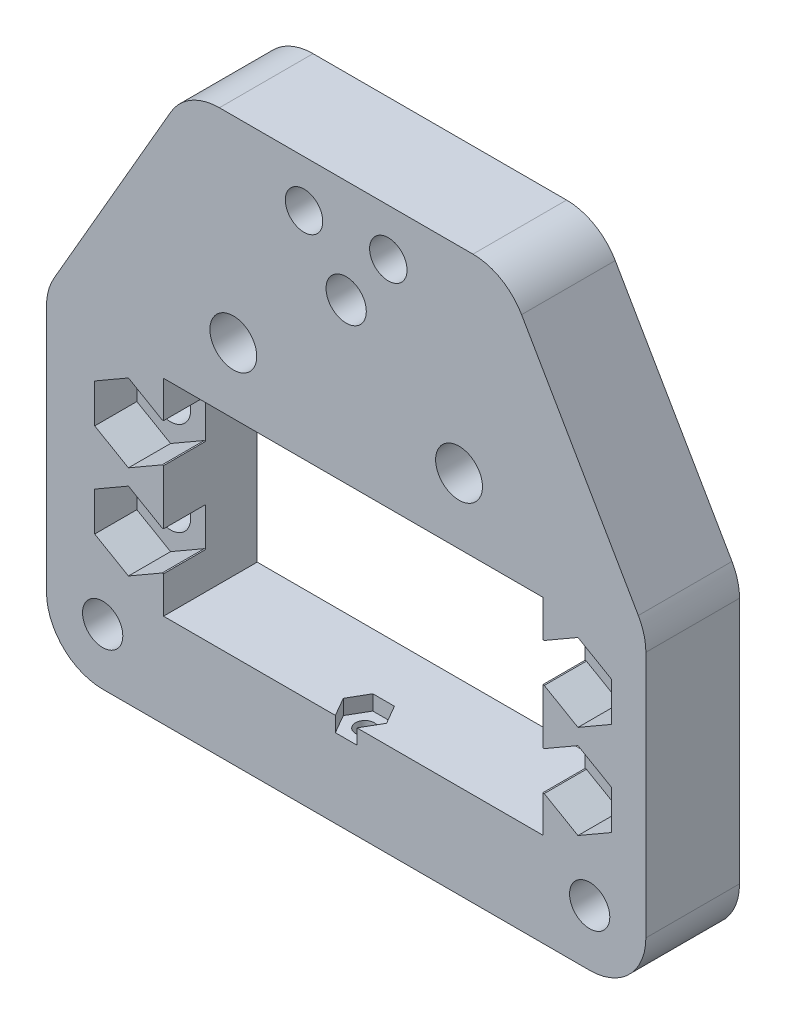
SolidWorks part; units mm, degrees
material "ABS"
ref_plane "Спереди" through (0, 0, 0) normal (0, 0, 1) x (1, 0, 0)
ref_plane "Сверху" through (0, 0, 0) normal (0, 1, 0) x (1, 0, 0)
ref_plane "Справа" through (0, 0, 0) normal (1, 0, 0) x (0, 0, -1)
sketch "Эскиз1" plane through (0, 0, 0) normal (0, 0, 1) x (1, 0, 0)
  line L0 (0, 0) -> (64, 0)
  line L1 (64, 0) -> (64, 34.0192)
  line L2 (64, 34.0192) -> (49, 60)
  line L3 (49, 60) -> (15, 60)
  line L4 (15, 60) -> (0, 34.02)
  line L5 (0, 34.02) -> (0, 0)
  dimension "D1" = 64
  dimension "D2" = 60
  dimension "D3" = 34
  dimension "D4" = 30
  dimension "D5" = 120
  dimension "D6" = 34.02
extrude "Бобышка-Вытянуть1" add sketch "Эскиз1" along normal blind 10 contours L0 L1 L2 L3 L4 L5
fillet "Скругление1" radius 6 6 edges at (49, 60, 5) (15, 60, 5) (0, 34.02, 5) (0, 0, 5) (64, 34.0192, 5) (64, 0, 5)
sketch "Эскиз2" plane through (0, 0, 10) normal (0, 0, 1) x (1, 0, 0)
  line L0 (12.5, 32) -> (53, 32)
  line L1 (53, 32) -> (53, 10)
  line L2 (53, 10) -> (12.5, 10)
  line L3 (12.5, 10) -> (12.5, 32)
  line L4 (64, 6) -> (64, 32.4115) construction
  line L5 (6, 0) -> (58, 0) construction
  dimension "D1" = 22
  dimension "D2" = 40.5
  dimension "D3" = 11
  dimension "D4" = 10
extrude "Вырез-Вытянуть1" cut sketch "Эскиз2" against normal through all
hole_wizard "Отверстия под штифты Ø4.0 мм1" positions "Эскиз3" profile "Эскиз4" hole size "Ø4.0" standard "Ansi Metric" end condition through all
sketch "Эскиз3" plane through (0, 0, 10) normal (0, 0, 1) x (1, 0, 0)
  line L0 (45.5359, 60) -> (18.4641, 60) construction
  line L1 (64, 6) -> (64, 32.4115) construction
  line L2 (32, 62.7032) -> (32, 49.5714) construction
  point P0 (27.4999, 55)
  point P2 (36.5, 55)
  point P13 (32, 60)
  dimension "D1" = 5
  dimension "D2" = 27.5
sketch "Эскиз4" plane through (27.4999, 55, 10) normal (1, 0, 0) x (0, -1, 0)
  line L0 (0, 0) -> (0, 10)
  line L1 (0, 10) -> (2, 10)
  line L2 (2, 10) -> (2, 0)
  line L5 (2, 0) -> (0, 0)
  line L11 (0, -6.35) -> (0, 13.871) construction
  dimension "Диаметр сквозного отверстия" = 4
  dimension "Глубина сквозного отверстия" = 10
hole_wizard "Отверстия под штифты Ø5.0 мм1" positions "Эскиз5" profile "Эскиз6" hole size "Ø5.0" standard "Ansi Metric" end condition through all
sketch "Эскиз5" plane through (0, 0, 10) normal (0, 0, 1) x (1, 0, 0)
  line L0 (45.5359, 60) -> (18.4641, 60) construction
  line L1 (64, 6) -> (64, 32.4115) construction
  line L2 (32, 62.5774) -> (32, 29.5493) construction
  point P0 (19.9499, 39)
  point P2 (44.05, 39)
  point P13 (32, 60)
  dimension "D1" = 21
  dimension "D2" = 19.95
sketch "Эскиз6" plane through (19.9499, 39, 10) normal (1, 0, 0) x (0, -1, 0)
  line L0 (0, 0) -> (0, 10)
  line L1 (0, 10) -> (2.5, 10)
  line L2 (2.5, 10) -> (2.5, 0)
  line L5 (2.5, 0) -> (0, 0)
  line L11 (0, -6.35) -> (0, 13.4589) construction
  dimension "Диаметр сквозного отверстия" = 5
  dimension "Глубина сквозного отверстия" = 10
hole_wizard "Сверло под метчик  спиральное M41" positions "Эскиз7" profile "Эскиз8" hole size "M4x0.7" standard "Ansi Metric" end condition through all
sketch "Эскиз7" plane through (0, 0, 10) normal (0, 0, 1) x (1, 0, 0)
  line L0 (53, 10) -> (53, 32) construction
  line L1 (53, 32) -> (12.5, 32) construction
  line L2 (32.75, 34.3929) -> (32.75, 8.0575) construction
  point P0 (56.75, 26)
  point P2 (56.75, 16)
  point P4 (8.75, 26)
  point P6 (8.75, 16)
  point P25 (32.75, 32)
  dimension "D1" = 3.75
  dimension "D2" = 6
  dimension "D3" = 10
sketch "Эскиз8" plane through (56.75, 26, 10) normal (1, 0, 0) x (0, -1, 0)
  line L0 (0, 0) -> (0, 10)
  line L1 (0, 10) -> (2.15, 10)
  line L2 (2.15, 10) -> (2.15, 0)
  line L5 (2.15, 0) -> (0, 0)
  line L11 (0, -6.35) -> (0, 14.6481) construction
  dimension "Диаметр сквозного отверстия" = 4.3
  dimension "Глубина сквозного отверстия" = 10
sketch "Эскиз9" plane through (0, 0, 10) normal (0, 0, -1) x (-1, 0, 0)
  line L0 (-56.75, 30.803) -> (-56.75, 10.8409) construction
  line L1 (-56.75, 30.1569) -> (-60.35, 28.0785)
  line L2 (-60.35, 28.0785) -> (-60.35, 23.9215)
  line L3 (-60.35, 23.9215) -> (-56.75, 21.8431)
  line L4 (-56.75, 21.8431) -> (-53.15, 23.9215)
  line L5 (-53.15, 23.9215) -> (-53.15, 28.0785)
  line L6 (-53.15, 28.0785) -> (-56.75, 30.1569)
  line L7 (-56.75, 20.1569) -> (-60.35, 18.0785)
  line L8 (-60.35, 18.0785) -> (-60.35, 13.9215)
  line L9 (-60.35, 13.9215) -> (-56.75, 11.8431)
  line L10 (-56.75, 11.8431) -> (-53.15, 13.9215)
  line L11 (-53.15, 13.9215) -> (-53.15, 18.0785)
  line L12 (-53.15, 18.0785) -> (-56.75, 20.1569)
  line L13 (-8.75, 30.1569) -> (-12.35, 28.0785)
  line L14 (-12.35, 28.0785) -> (-12.35, 23.9215)
  line L15 (-12.35, 23.9215) -> (-8.75, 21.8431)
  line L16 (-8.75, 21.8431) -> (-5.15, 23.9215)
  line L17 (-5.15, 23.9215) -> (-5.15, 28.0785)
  line L18 (-5.15, 28.0785) -> (-8.75, 30.1569)
  line L19 (-8.75, 20.1569) -> (-12.35, 18.0785)
  line L20 (-12.35, 18.0785) -> (-12.35, 13.9215)
  line L21 (-12.35, 13.9215) -> (-8.75, 11.8431)
  line L22 (-8.75, 11.8431) -> (-5.15, 13.9215)
  line L23 (-5.15, 13.9215) -> (-5.15, 18.0785)
  line L24 (-5.15, 18.0785) -> (-8.75, 20.1569)
  line L25 (-8.75, 30.803) -> (-8.75, 11.1079) construction
  circle A0 centre (-56.75, 26) radius 3.6 construction
  circle A1 centre (-56.75, 16) radius 3.6 construction
  circle A2 centre (-8.75, 26) radius 3.6 construction
  circle A3 centre (-8.75, 16) radius 3.6 construction
  dimension "D1" = 7.2
  dimension "D2" = 7.2
  dimension "D3" = 7.2
  dimension "D4" = 7.2
  dimension "D5" = 60
  dimension "D6" = 60
  dimension "D7" = 60
  dimension "D8" = 60
extrude "Вырез-Вытянуть4" cut sketch "Эскиз9" along normal blind 4.5
sketch "Эскиз12" plane through (0, 10, 0) normal (0, 1, 0) x (1, 0, 0)
  line L0 (32, 0.39) -> (32, -4.7781) construction
  line L7 (45.5359, 0) -> (18.4641, 0) construction
  line L9 (34.3094, -8) -> (33.1547, -6)
  line L10 (33.1547, -6) -> (30.8453, -6)
  line L11 (30.8453, -6) -> (29.6906, -8)
  line L12 (29.6906, -8) -> (30.8453, -10)
  line L13 (30.8453, -10) -> (33.1547, -10)
  line L14 (33.1547, -10) -> (34.3094, -8)
  circle A1 centre (32, -8) radius 2 construction
  point P12 (32, 0)
  dimension "D1" = 4
  dimension "D2" = 8
  dimension "D3" = 30
hole_wizard "Сверло под метчик  спиральное M42" positions "Эскиз16" profile "Эскиз17" hole size "M4x0.7" standard "Ansi Metric" end condition through all
sketch "Эскиз16" plane through (0, 0, 10) normal (0, 0, 1) x (1, 0, 0)
  line L0 (45.5359, 60) -> (18.4641, 60) construction
  line L1 (64, 6) -> (64, 32.4115) construction
  line L2 (6, 0) -> (58, 0) construction
  line L3 (32, -2.539) -> (32, 12.8188) construction
  point P0 (32, 49)
  point P2 (6, 6)
  point P4 (58, 6)
  point P19 (32, 0)
  dimension "D1" = 11
  dimension "D2" = 32
  dimension "D3" = 6
  dimension "D4" = 6
sketch "Эскиз17" plane through (32, 49, 10) normal (1, 0, 0) x (0, -1, 0)
  line L0 (0, 0) -> (0, 10)
  line L1 (0, 10) -> (2.15, 10)
  line L2 (2.15, 10) -> (2.15, 0)
  line L5 (2.15, 0) -> (0, 0)
  line L11 (0, -6.35) -> (0, 15.6845) construction
  dimension "Диаметр сквозного отверстия" = 4.3
  dimension "Глубина сквозного отверстия" = 10
sketch "Эскиз18" plane through (0, 0, 0) normal (0, 0, -1) x (-1, 0, 0)
  line L0 (-32, 53.874) -> (-32, 44.3135) construction
  line L1 (-32, 53.1569) -> (-35.6, 51.0785)
  line L2 (-35.6, 51.0785) -> (-35.6, 46.9215)
  line L3 (-35.6, 46.9215) -> (-32, 44.8431)
  line L4 (-32, 44.8431) -> (-28.4, 46.9215)
  line L5 (-28.4, 46.9215) -> (-28.4, 51.0785)
  line L6 (-28.4, 51.0785) -> (-32, 53.1569)
  line L7 (-58, 10.1569) -> (-61.6, 8.0785)
  line L8 (-61.6, 8.0785) -> (-61.6, 3.9215)
  line L9 (-61.6, 3.9215) -> (-58, 1.8431)
  line L10 (-58, 1.8431) -> (-54.4, 3.9215)
  line L11 (-54.4, 3.9215) -> (-54.4, 8.0785)
  line L12 (-54.4, 8.0785) -> (-58, 10.1569)
  line L13 (-6, 10.1569) -> (-9.6, 8.0785)
  line L14 (-9.6, 8.0785) -> (-9.6, 3.9215)
  line L15 (-9.6, 3.9215) -> (-6, 1.8431)
  line L16 (-6, 1.8431) -> (-2.4, 3.9215)
  line L17 (-2.4, 3.9215) -> (-2.4, 8.0785)
  line L18 (-2.4, 8.0785) -> (-6, 10.1569)
  line L19 (-58, 11.3834) -> (-58, 0.9026) construction
  line L20 (-6, 11.3834) -> (-6, 0.9026) construction
  circle A0 centre (-32, 49) radius 3.6 construction
  circle A1 centre (-58, 6) radius 3.6 construction
  circle A2 centre (-6, 6) radius 3.6 construction
  dimension "D1" = 7.2
  dimension "D2" = 7.2
  dimension "D3" = 7.2
  dimension "D4" = 60
  dimension "D5" = 60
  dimension "D6" = 60
extrude "Вырез-Вытянуть7" cut sketch "Эскиз18" against normal blind 3.2
sketch "Эскиз19" plane through (53, 0, 0) normal (-1, 0, 0) x (0, 0, 1)
  line L0 (10, 28.0785) -> (5.5, 28.0785)
  line L1 (10, 10) -> (10, 32) construction
  line L2 (5.5, 28.0785) -> (5.5, 23.9215)
  line L3 (5.5, 23.9215) -> (10, 23.9215)
  line L4 (10, 23.9215) -> (10, 28.0785)
  dimension "D1" = 4.5
extrude "Вырез-Вытянуть13" cut sketch "Эскиз19" against normal blind 0.15 contours L3 L4 L0 L2
sketch "Эскиз21" plane through (12.5, 0, 0) normal (1, 0, 0) x (0, 0, -1)
  line L0 (-10, 28.0785) -> (-5.5, 28.0785)
  line L1 (-10, 32) -> (-10, 10) construction
  line L2 (-5.5, 28.0785) -> (-5.5, 23.9215)
  line L3 (-5.5, 23.9215) -> (-10, 23.9215)
  line L4 (-10, 23.9215) -> (-10, 28.0785)
  dimension "D1" = 4.5
extrude "Вырез-Вытянуть14" cut sketch "Эскиз21" against normal blind 0.15
sketch "Эскиз22" plane through (53, 0, 0) normal (-1, 0, 0) x (0, 0, 1)
  line L0 (10, 18.0785) -> (5.5, 18.0785)
  line L1 (10, 10) -> (10, 23.9215) construction
  line L2 (5.5, 18.0785) -> (5.5, 13.9215)
  line L3 (5.5, 13.9215) -> (10, 13.9215)
  line L4 (10, 13.9215) -> (10, 18.0785)
  dimension "D1" = 4.5
extrude "Вырез-Вытянуть15" cut sketch "Эскиз22" against normal blind 0.15
sketch "Эскиз23" plane through (12.5, 0, 0) normal (1, 0, 0) x (0, 0, -1)
  line L0 (-10, 18.0785) -> (-5.5, 18.0785)
  line L1 (-10, 23.9215) -> (-10, 10) construction
  line L2 (-5.5, 18.0785) -> (-5.5, 13.9215)
  line L3 (-5.5, 13.9215) -> (-10, 13.9215)
  line L4 (-10, 13.9215) -> (-10, 18.0785)
  dimension "D1" = 4.5
extrude "Вырез-Вытянуть16" cut sketch "Эскиз23" against normal blind 0.15
extrude "Вырез-Вытянуть17" cut sketch "Эскиз12" against normal blind 1.6 contours L12 L13 L14 L9 L10 L11
hole_wizard "Сверло под метчик  спиральное M2.21" positions "Эскиз24" profile "Эскиз25" hole size "M2.2x0.45" standard "Ansi Metric"
sketch "Эскиз24" plane through (0, 0, 0) normal (0, -1, 0) x (-1, 0, 0)
  line L0 (-6, 0) -> (-58, 0) construction
  line L1 (-6, -10) -> (-6, 0) construction
  point P0 (-32, -8)
  dimension "D1" = 8
  dimension "D2" = 26
sketch "Эскиз25" plane through (32, 0, 8) normal (1, 0, 0) x (0, 0, -1)
  line L0 (0, 0) -> (0, 10.6009)
  line L1 (0, 10.6009) -> (1, 10)
  line L2 (1, 10) -> (1, 0)
  line L5 (1, 0) -> (0, 0)
  line L10 (0, 10.6009) -> (-1, 10) construction
  line L11 (0, -4.9654) -> (0, 14.7206) construction
  dimension "Диаметр отверстия" = 2
  dimension "Глубина отверстия" = 10
  dimension "Угол заточки сверла" = 118
